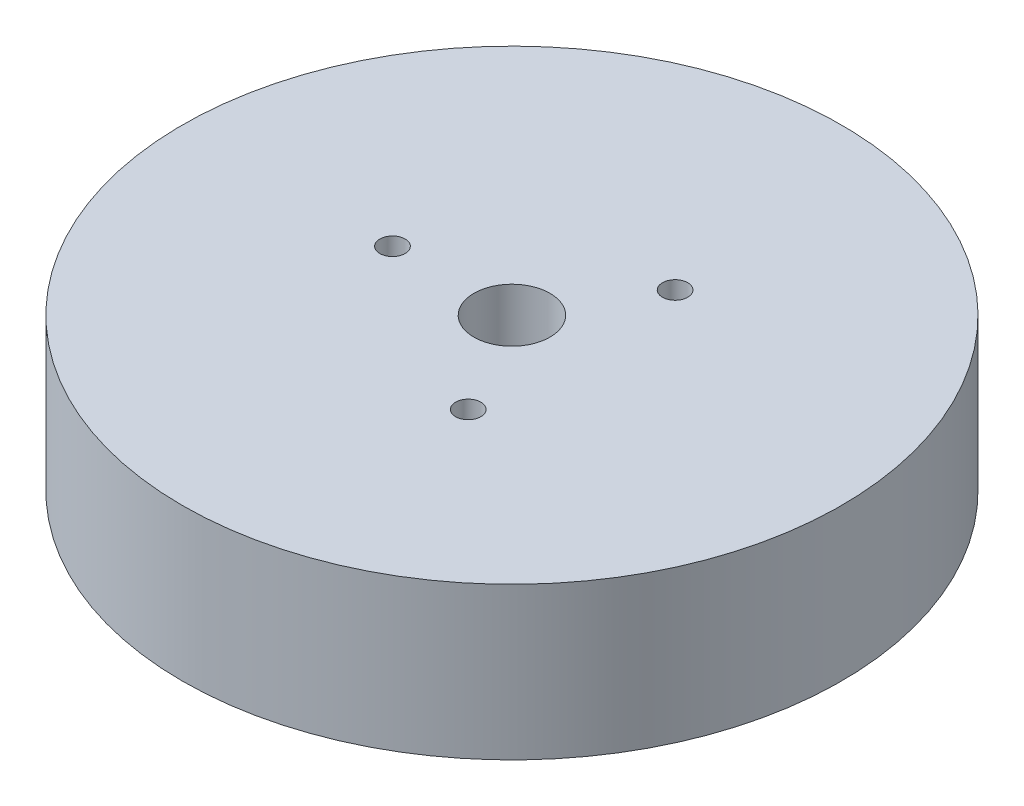
SolidWorks part; units mm, degrees
ref_plane "Front Plane" through (0, 0, 0) normal (0, 0, 1) x (1, 0, 0)
ref_plane "Top Plane" through (0, 0, 0) normal (0, 1, 0) x (1, 0, 0)
ref_plane "Right Plane" through (0, 0, 0) normal (1, 0, 0) x (0, 0, -1)
sketch "Sketch1" plane through (0, 0, 0) normal (0, 1, 0) x (1, 0, 0)
  circle A0 centre (0, 0) radius 65
  dimension "FLANGE_OD" = 130
extrude "Boss-Extrude1" add sketch "Sketch1" along normal blind 30
sketch "Sketch2" plane through (0, 0, 0) normal (0, 1, 0) x (1, 0, 0)
  circle A0 centre (0, 0) radius 7.5
  dimension "BORE_D" = 15
extrude "Cut-Extrude1" cut sketch "Sketch2" along normal through all
sketch "Sketch3" plane through (0, 30, 0) normal (0, 1, 0) x (1, 0, 0)
  circle A0 centre (0, 0) radius 23.5564 construction
  circle A1 centre (-23.5564, 0) radius 2.4913
  dimension "BOLT_D" = 4.9827
  dimension "BOLT_PCD" = 47.1127
extrude "Cut-Extrude2" cut sketch "Sketch3" against normal blind 27.3807
pattern_circular "CirPattern1" count 3 over 360 about axis through (0, 0, 0) along (0, 1, 0) of "Cut-Extrude2"
